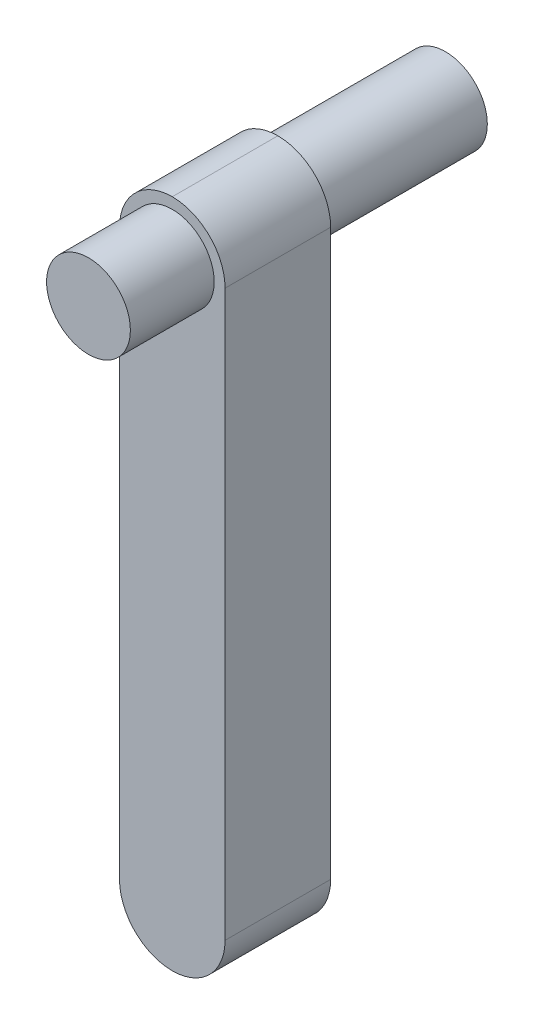
SolidWorks part; units mm, degrees
ref_plane "Front Plane" through (0, 0, 0) normal (0, 0, 1) x (1, 0, 0)
ref_plane "Top Plane" through (0, 0, 0) normal (0, 1, 0) x (1, 0, 0)
ref_plane "Right Plane" through (0, 0, 0) normal (1, 0, 0) x (0, 0, -1)
sketch "Sketch1" plane through (0, 0, 0) normal (0, 0, 1) x (1, 0, 0)
  line L1 (-4, 25.4) -> (4, 25.4)
  line L2 (-4, 25.4) -> (-4, -25.4)
  line L3 (-4, -25.4) -> (4, -25.4)
  line L4 (4, 25.4) -> (4, -25.4)
  line L5 (-4, 25.4) -> (4, -25.4) construction
  line L6 (-4, -25.4) -> (4, 25.4) construction
  point P0 (0, 0)
  dimension "D1" = 8
  dimension "D2" = 50.8
extrude "Boss-Extrude1" add sketch "Sketch1" along normal blind 8
fillet "Fillet1" radius 4 4 edges at (-4, -25.4, 4) (4, -25.4, 4) (-4, 25.4, 4) (4, 25.4, 4)
sketch "Sketch2" plane through (0, 0, 8) normal (0, 0, 1) x (1, 0, 0)
  circle A0 centre (0, 21.4) radius 3.175
  arc A1 (4, 21.4) -> (0, 25.4) centre (0, 21.4) ccw construction
  dimension "D1" = 6.35
extrude "Boss-Extrude2" add sketch "Sketch2" along normal blind 6.35 and the other way blind 20.7
